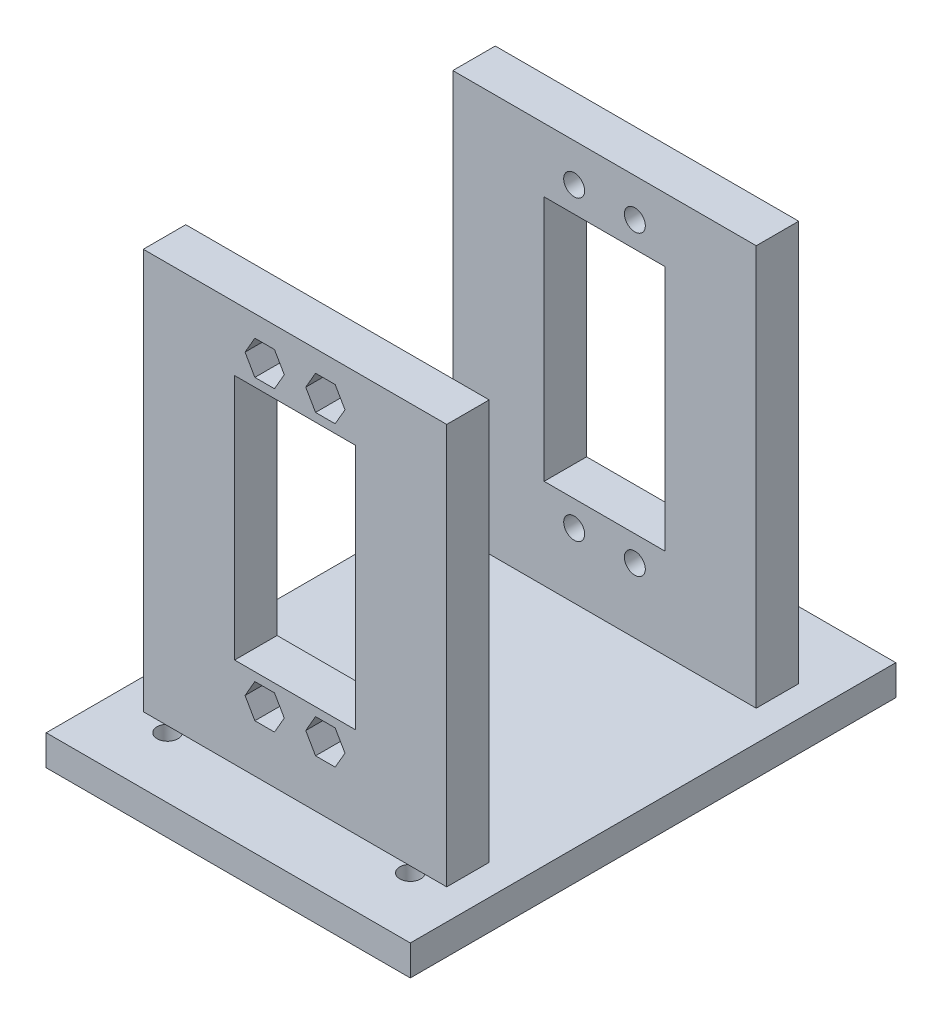
SolidWorks part; units mm, degrees
material "PLA Makeshift"
ref_plane "Front Plane" through (0, 0, 0) normal (0, 0, 1) x (1, 0, 0)
ref_plane "Top Plane" through (0, 0, 0) normal (0, 1, 0) x (1, 0, 0)
ref_plane "Right Plane" through (0, 0, 0) normal (1, 0, 0) x (0, 0, -1)
sketch "Sketch1" plane through (0, 0, 0) normal (0, 1, 0) x (1, 0, 0)
  line L1 (-30, -40) -> (30, -40)
  line L2 (-30, -40) -> (-30, 40)
  line L3 (-30, 40) -> (30, 40)
  line L4 (30, -40) -> (30, 40)
  line L5 (-30, -40) -> (30, 40) construction
  line L6 (-30, 40) -> (30, -40) construction
  point P0 (0, 0)
  dimension "D1" = 80
  dimension "D2" = 60
extrude "Boss-Extrude1" add sketch "Sketch1" along normal mid plane 5
sketch "Sketch2" plane through (0, 2.5, 0) normal (0, 1, 0) x (1, 0, 0)
  line L0 (30, -40) -> (30, 40) construction
  line L2 (-30, 40) -> (-30, -40) construction
  line L3 (-30, -40) -> (30, -40) construction
  circle A0 centre (-20, 30) radius 1.725
  circle A1 centre (20, 30) radius 1.725
  circle A2 centre (20, -30) radius 1.725
  circle A3 centre (-20, -30) radius 1.725
  dimension "D1" = 3.45
  dimension "D2" = 40
  dimension "D3" = 10
  dimension "D4" = 60
  dimension "D5" = 60
  dimension "D6" = 40
  dimension "D7" = 10
  dimension "D8" = 10
  dimension "D9" = 10
extrude "Cut-Extrude1" cut sketch "Sketch2" against normal through all
ref_plane "Plane1" through (0, 0, 22) normal (0, 0, 1) x (1, 0, 0)
sketch "Sketch3" plane through (0, 0, 22) normal (0, 0, 1) x (1, 0, 0)
  line L1 (-25, 2.5) -> (25, 2.5)
  line L2 (-25, 2.5) -> (-25, 68.5)
  line L3 (-25, 68.5) -> (25, 68.5)
  line L4 (25, 2.5) -> (25, 68.5)
  dimension "D1" = 50
  dimension "D2" = 25
  dimension "D3" = 66
  dimension "D4" = 2.5
extrude "Boss-Extrude2" add sketch "Sketch3" along normal blind 7
mirror "Mirror1" about plane through (0, 0, 0) normal (0, 0, 1) of "Boss-Extrude2"
sketch "Sketch4" plane through (0, 0, 29) normal (0, 0, 1) x (1, 0, 0)
  line L1 (-9.95, 58) -> (9.95, 58)
  line L2 (-9.95, 58) -> (-9.95, 17.4)
  line L3 (-9.95, 17.4) -> (9.95, 17.4)
  line L4 (9.95, 58) -> (9.95, 17.4)
  dimension "D1" = 19.9
  dimension "D2" = 9.95
  dimension "D3" = 40.6
  dimension "D4" = 17.4
extrude "Cut-Extrude2" cut sketch "Sketch4" against normal through all
sketch "Sketch5" plane through (0, 0, 29) normal (0, 0, 1) x (1, 0, 0)
  circle A0 centre (-5, 62.2) radius 1.725
  circle A1 centre (5, 62.2) radius 1.725
  circle A2 centre (-5, 13.2) radius 1.725
  circle A3 centre (5, 13.2) radius 1.725
  dimension "D9" = 3.45
  dimension "D1" = 5
  dimension "D2" = 5
  dimension "D3" = 13.2
  dimension "D4" = 13.2
  dimension "D5" = 62.2
  dimension "D6" = 62.2
  dimension "D7" = 5
  dimension "D8" = 5
extrude "Cut-Extrude3" cut sketch "Sketch5" against normal through all
sketch "Sketch6" plane through (0, 0, 29) normal (0, 0, 1) x (1, 0, 0)
  line L1 (-1.7668, 62.2) -> (-3.3834, 65)
  line L2 (-3.3834, 65) -> (-6.6166, 65)
  line L3 (-6.6166, 65) -> (-8.2332, 62.2)
  line L4 (-8.2332, 62.2) -> (-6.6166, 59.4)
  line L5 (-6.6166, 59.4) -> (-3.3834, 59.4)
  line L6 (-3.3834, 59.4) -> (-1.7668, 62.2)
  line L7 (1.7668, 62.2) -> (3.3834, 59.4)
  line L8 (3.3834, 59.4) -> (6.6166, 59.4)
  line L9 (6.6166, 59.4) -> (8.2332, 62.2)
  line L10 (8.2332, 62.2) -> (6.6166, 65)
  line L11 (6.6166, 65) -> (3.3834, 65)
  line L12 (3.3834, 65) -> (1.7668, 62.2)
  line L13 (-1.7668, 13.2) -> (-3.3834, 16)
  line L14 (-3.3834, 16) -> (-6.6166, 16)
  line L15 (-6.6166, 16) -> (-8.2332, 13.2)
  line L16 (-8.2332, 13.2) -> (-6.6166, 10.4)
  line L17 (-6.6166, 10.4) -> (-3.3834, 10.4)
  line L18 (-3.3834, 10.4) -> (-1.7668, 13.2)
  line L19 (8.2332, 13.2) -> (6.6166, 16)
  line L20 (6.6166, 16) -> (3.3834, 16)
  line L21 (3.3834, 16) -> (1.7668, 13.2)
  line L22 (1.7668, 13.2) -> (3.3834, 10.4)
  line L23 (3.3834, 10.4) -> (6.6166, 10.4)
  line L24 (6.6166, 10.4) -> (8.2332, 13.2)
  circle A0 centre (-5, 62.2) radius 2.8 construction
  circle A1 centre (5, 62.2) radius 2.8 construction
  circle A2 centre (-5, 13.2) radius 2.8 construction
  circle A3 centre (5, 13.2) radius 2.8 construction
extrude "Cut-Extrude4" cut sketch "Sketch6" against normal blind 4.2
mirror "Mirror3" about plane through (0, 0, 0) normal (0, 0, 1) of "Cut-Extrude4"
